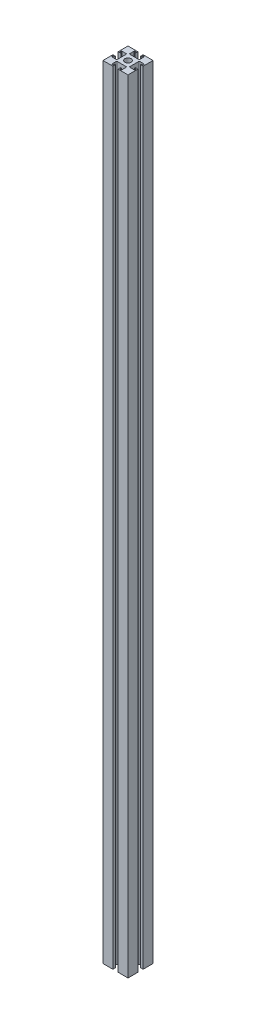
SolidWorks part; units mm, degrees
ref_plane "Plano frontal" through (0, 0, 0) normal (0, 0, 1) x (1, 0, 0)
ref_plane "Plano superior" through (0, 0, 0) normal (0, 1, 0) x (1, 0, 0)
ref_plane "Plano direito" through (0, 0, 0) normal (1, 0, 0) x (0, 0, -1)
sketch "Esboço2" plane through (0, 0, 0) normal (0, 1, 0) x (1, 0, 0)
  line L0 (-1.8037, 6.5679) -> (2.6963, 6.5679)
  line L1 (-1.8037, -17.5821) -> (38.1963, -17.5821)
  line L2 (-1.8037, -17.5821) -> (-1.8037, 22.4179)
  line L3 (-1.8037, 22.4179) -> (38.1963, 22.4179)
  line L4 (38.1963, -17.5821) -> (38.1963, 22.4179)
  line L5 (2.6963, 6.5679) -> (2.6963, 7.9179)
  line L6 (2.2188, 10.4179) -> (7.2188, 10.4179)
  line L7 (8.2188, 9.4179) -> (8.2188, -4.5821)
  line L8 (7.2188, -5.5821) -> (2.2188, -5.5821)
  line L9 (2.2188, -5.5821) -> (0.7188, -5.5821)
  line L10 (2.6963, -1.7321) -> (-1.8037, -1.7321)
  line L11 (0.7188, 10.4179) -> (2.2188, 10.4179)
  line L12 (2.6963, -1.7321) -> (2.6963, -3.0821)
  line L13 (2.6963, 7.9179) -> (-0.2812, 7.9179)
  line L14 (-0.2812, 7.9179) -> (-0.2812, 9.4179)
  line L15 (2.6963, -3.0821) -> (-0.2812, -3.0821)
  line L16 (-0.2812, -3.0821) -> (-0.2812, -4.5821)
  line L17 (-1.8037, 6.5679) -> (-1.8037, -1.7321)
  line L18 (18.1963, 22.4179) -> (18.1963, -17.5821) construction
  line L19 (-1.8037, 2.4179) -> (38.1963, 2.4179) construction
  line L20 (38.1963, 6.5679) -> (38.1963, -1.7321)
  line L21 (36.6737, -3.0821) -> (36.6737, -4.5821)
  line L22 (33.6963, -3.0821) -> (36.6737, -3.0821)
  line L23 (36.6737, 7.9179) -> (36.6737, 9.4179)
  line L24 (33.6963, 7.9179) -> (36.6737, 7.9179)
  line L25 (33.6963, -1.7321) -> (33.6963, -3.0821)
  line L26 (35.6737, 10.4179) -> (34.1737, 10.4179)
  line L27 (33.6963, -1.7321) -> (38.1963, -1.7321)
  line L28 (34.1737, -5.5821) -> (35.6737, -5.5821)
  line L29 (29.1737, -5.5821) -> (34.1737, -5.5821)
  line L30 (28.1737, 9.4179) -> (28.1737, -4.5821)
  line L31 (34.1737, 10.4179) -> (29.1737, 10.4179)
  line L32 (33.6963, 6.5679) -> (33.6963, 7.9179)
  line L33 (38.1963, 6.5679) -> (33.6963, 6.5679)
  arc A0 (0.7188, 10.4179) -> (-0.2812, 9.4179) centre (0.7188, 9.4179) ccw
  arc A1 (0.7188, -5.5821) -> (-0.2812, -4.5821) centre (0.7188, -4.5821) cw
  arc A2 (8.2188, 9.4179) -> (7.2188, 10.4179) centre (7.2188, 9.4179) ccw
  arc A3 (7.2188, -5.5821) -> (8.2188, -4.5821) centre (7.2188, -4.5821) ccw
  arc A4 (29.1737, -5.5821) -> (28.1737, -4.5821) centre (29.1737, -4.5821) cw
  arc A5 (28.1737, 9.4179) -> (29.1737, 10.4179) centre (29.1737, 9.4179) cw
  arc A6 (35.6737, -5.5821) -> (36.6737, -4.5821) centre (35.6737, -4.5821) ccw
  arc A7 (35.6737, 10.4179) -> (36.6737, 9.4179) centre (35.6737, 9.4179) cw
  circle A8 centre (18.1963, 2.4179) radius 5
  point P22 (-0.2812, -5.5821)
  point P25 (8.2188, 10.4179)
  point P28 (8.2188, -5.5821)
  point P29 (-1.8037, 2.4179)
  point P30 (-1.8037, 2.4179)
  point P57 (28.1737, -5.5821)
  point P58 (28.1737, 10.4179)
  point P59 (36.6737, -5.5821)
  point P62 (18.1963, -17.5821)
  line B0 (14.0463, -17.5821) -> (14.0463, -13.0821)
  line B1 (14.0463, -13.0821) -> (12.6963, -13.0821)
  line B2 (10.1963, -13.5595) -> (10.1963, -8.5595)
  line B3 (11.1963, -7.5595) -> (25.1963, -7.5595)
  line B4 (26.1963, -8.5595) -> (26.1963, -13.5595)
  line B5 (26.1963, -13.5595) -> (26.1963, -15.0595)
  line B6 (22.3463, -13.0821) -> (22.3463, -17.5821)
  line B7 (10.1963, -15.0595) -> (10.1963, -13.5595)
  line B8 (22.3463, -13.0821) -> (23.6963, -13.0821)
  line B9 (12.6963, -13.0821) -> (12.6963, -16.0595)
  line B10 (12.6963, -16.0595) -> (11.1963, -16.0595)
  line B11 (23.6963, -13.0821) -> (23.6963, -16.0595)
  line B12 (23.6963, -16.0595) -> (25.1963, -16.0595)
  line B13 (14.0463, -17.5821) -> (22.3463, -17.5821)
  arc B14 (10.1963, -15.0595) -> (11.1963, -16.0595) centre (11.1963, -15.0595) ccw
  arc B15 (26.1963, -15.0595) -> (25.1963, -16.0595) centre (25.1963, -15.0595) cw
  arc B16 (11.1963, -7.5595) -> (10.1963, -8.5595) centre (11.1963, -8.5595) ccw
  arc B17 (26.1963, -8.5595) -> (25.1963, -7.5595) centre (25.1963, -8.5595) ccw
  line B18 (14.0463, 22.4179) -> (14.0463, 17.9179)
  line B19 (14.0463, 17.9179) -> (12.6963, 17.9179)
  line B20 (10.1963, 18.3954) -> (10.1963, 13.3954)
  line B21 (11.1963, 12.3954) -> (25.1963, 12.3954)
  line B22 (26.1963, 13.3954) -> (26.1963, 18.3954)
  line B23 (26.1963, 18.3954) -> (26.1963, 19.8954)
  line B24 (22.3463, 17.9179) -> (22.3463, 22.4179)
  line B25 (10.1963, 19.8954) -> (10.1963, 18.3954)
  line B26 (22.3463, 17.9179) -> (23.6963, 17.9179)
  line B27 (12.6963, 17.9179) -> (12.6963, 20.8954)
  line B28 (12.6963, 20.8954) -> (11.1963, 20.8954)
  line B29 (23.6963, 17.9179) -> (23.6963, 20.8954)
  line B30 (23.6963, 20.8954) -> (25.1963, 20.8954)
  line B31 (14.0463, 22.4179) -> (22.3463, 22.4179)
  arc B32 (10.1963, 19.8954) -> (11.1963, 20.8954) centre (11.1963, 19.8954) cw
  arc B33 (26.1963, 19.8954) -> (25.1963, 20.8954) centre (25.1963, 19.8954) ccw
  arc B34 (11.1963, 12.3954) -> (10.1963, 13.3954) centre (11.1963, 13.3954) cw
  arc B35 (26.1963, 13.3954) -> (25.1963, 12.3954) centre (25.1963, 13.3954) cw
  dimension "D8" = 2.5
  dimension "D10" = 1
  dimension "D11" = 1
  dimension "D12" = 1
  dimension "D13" = 10
  dimension "D1" = 40
  dimension "D2" = 40
  dimension "D3" = 8.3
  dimension "D4" = 6
  dimension "D5" = 4.5
  dimension "D6" = 1.35
  dimension "D7" = 16
  dimension "D9" = 2.5
sketch_block_instance "Bloco1-1"
sketch_block "Bloco1" parameters "D2"=1, "D3"=1, "D1"=2.5
sketch_block_instance "Bloco1-2"
extrude "Ressalto-extrusão1" add sketch "Esboço2" along normal blind 1250 contours B22 B35 B21 B34 B20 B25 B32 B28 B27 B19 B18 L3 L2 L0 L5 L13 L14 A0 L11 L6 A2 L7 A3 L8 L9 A1 L16 L15 L12 L10 L1 B0 B1 B9 B10 B14 B7 B2 B16 B3 B17 B4 B5 B15 B12 B11 B8 B6 L4 | A8 region at (-1.238, 0, -14.4929) region at (18.1963, 0, -2.4179)
extrude "Corte-extrusão1" cut sketch "Esboço2<3>" along normal blind 10 contours A8
sketch "Esboço2<3>" plane through (0, 0, 0) normal (0, 1, 0) x (1, 0, 0) same geometry as "Esboço2"
sketch "Esboço4" plane through (0, 1250, 0) normal (0, 1, 0) x (1, 0, 0)
  line L0 (8.2188, 2.4179) -> (28.1737, 2.4179) construction
  line L1 (8.2188, 9.4179) -> (8.2188, -4.5821) construction
  line L2 (28.1737, 9.4179) -> (28.1737, -4.5821) construction
  line L3 (11.1963, 12.3954) -> (25.1963, 12.3954) construction
  line L4 (18.1963, 12.3954) -> (18.1963, -7.5595) construction
  line L5 (11.1963, -7.5595) -> (25.1963, -7.5595) construction
  circle A0 centre (18.1963, 2.4179) radius 5
  dimension "D1" = 10
extrude "Corte-extrusão2" cut sketch "Esboço4" against normal blind 20
